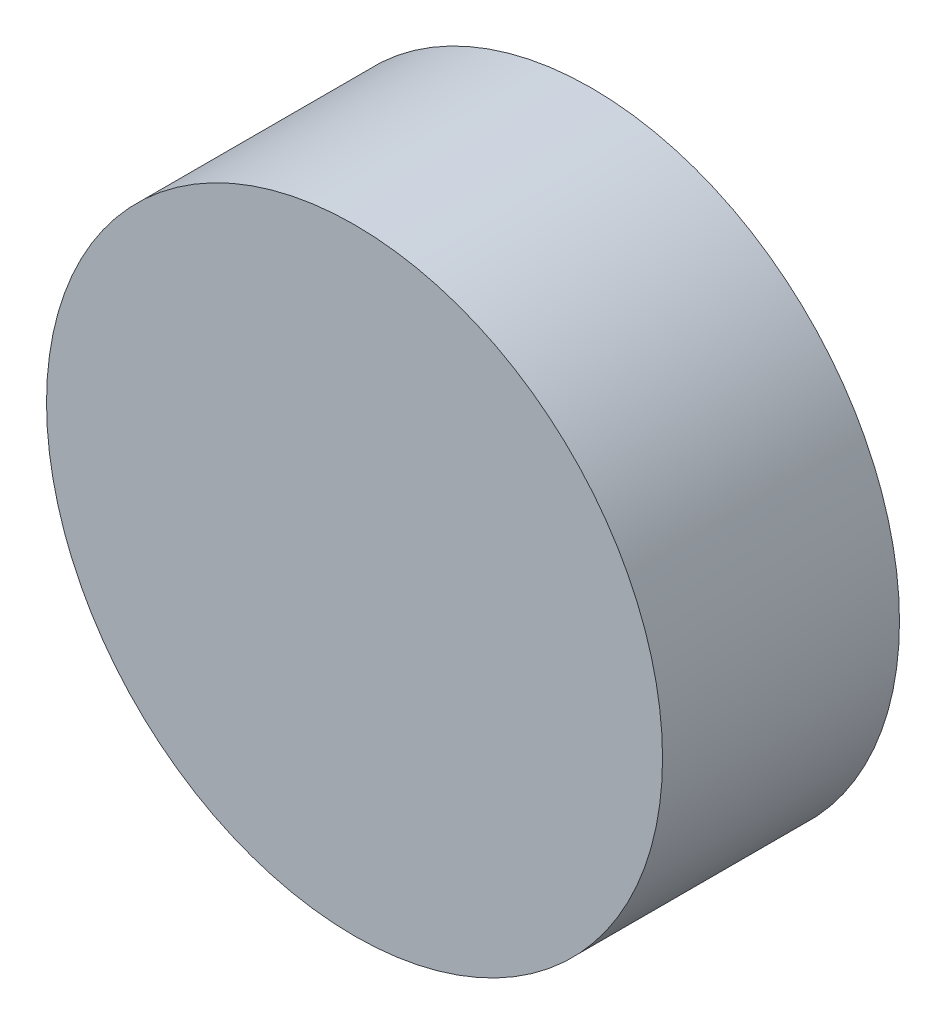
SolidWorks part; units mm, degrees
ref_plane "Спереди" through (0, 0, 0) normal (0, 0, 1) x (1, 0, 0)
ref_plane "Сверху" through (0, 0, 0) normal (0, 1, 0) x (1, 0, 0)
ref_plane "Справа" through (0, 0, 0) normal (1, 0, 0) x (0, 0, -1)
sketch "Эскиз1" plane through (0, 0, 0) normal (0, 0, 1) x (1, 0, 0)
  circle A0 centre (0, 0) radius 32.5
extrude "CS_RIGHT_WHEEL" add sketch "Эскиз1" along normal blind 25
ref_axis "AXIS_RIGHT_WHEEL" through (0, 0, 25) along (0, 0, -1)
